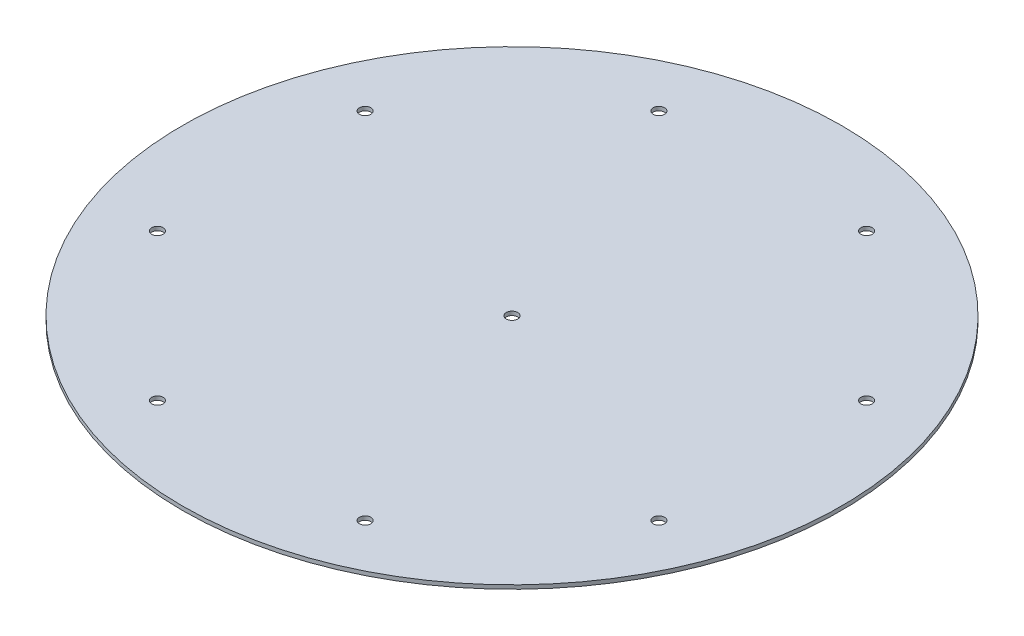
SolidWorks part; units mm, degrees
ref_plane "Front Plane" through (0, 0, 0) normal (0, 0, 1) x (1, 0, 0)
ref_plane "Top Plane" through (0, 0, 0) normal (0, 1, 0) x (1, 0, 0)
ref_plane "Right Plane" through (0, 0, 0) normal (1, 0, 0) x (0, 0, -1)
sketch "Sketch2" plane through (0, 0, 0) normal (1, 0, 0) x (0, 0, -1)
  line L0 (0, 0) -> (-84.9998, 0)
  line L1 (-84.9998, 0) -> (-84.9998, 1)
  line L2 (-84.9998, 1) -> (0, 1)
  line L5 (0, 1) -> (0, 0)
  point P3 (0, 0)
  dimension "D1" = 84.9998
  dimension "D2" = 1
ref_axis "Axis1" through (0, -0.75, 0) along (0, 1, 0)
revolve "Revolve1" add sketch "Sketch2" angle 360 about axis through (0, -0.75, 0) along (0, 1, 0)
hole_wizard "#32 (0.116) Diameter Hole1" positions "Sketch6" profile "Sketch7" hole size "#32" standard "ANSI Inch" end condition through all
sketch "Sketch6" plane through (0, 1, 0) normal (0, 1, 0) x (1, 0, 0)
  line L0 (0, 0) -> (-53.438, 129.0108) construction
  line L2 (0, 0) -> (0, 109.0908) construction
  point P0 (-26.7878, 64.6716)
  dimension "D1" = 22.5
  dimension "D2" = 70
sketch "Sketch7" plane through (-26.7878, 1, -64.6716) normal (1, 0, 0) x (0, 0, 1)
  line L0 (0, 0) -> (0, 1)
  line L1 (0, 1) -> (1.4732, 1)
  line L2 (1.4732, 1) -> (1.4732, 0)
  line L5 (1.4732, 0) -> (0, 0)
  line L11 (0, -6.35) -> (0, 107.95) construction
  dimension "Thru Hole Dia." = 2.9464
  dimension "Thru Hole Depth" = 1
pattern_circular "CirPattern3" count 8 over 360 about axis through (0, -0.75, 0) along (0, 1, 0) of "#32 (0.116) Diameter Hole1"
hole_wizard "#32 (0.116) Diameter Hole2" positions "Sketch8" profile "Sketch9" hole size "#32" standard "ANSI Inch" end condition through all
sketch "Sketch8" plane through (0, 1, 0) normal (0, 1, 0) x (1, 0, 0)
  line L0 (0, 0) -> (106.3094, -1.7118) construction
  point P7 (0, 0)
sketch "Sketch9" plane through (0, 1, 0) normal (1, 0, 0) x (0, 0, 1)
  line L0 (0, 0) -> (0, 1)
  line L1 (0, 1) -> (1.4732, 1)
  line L2 (1.4732, 1) -> (1.4732, 0)
  line L5 (1.4732, 0) -> (0, 0)
  line L11 (0, -6.35) -> (0, 107.95) construction
  dimension "Thru Hole Dia." = 2.9464
  dimension "Thru Hole Depth" = 1
